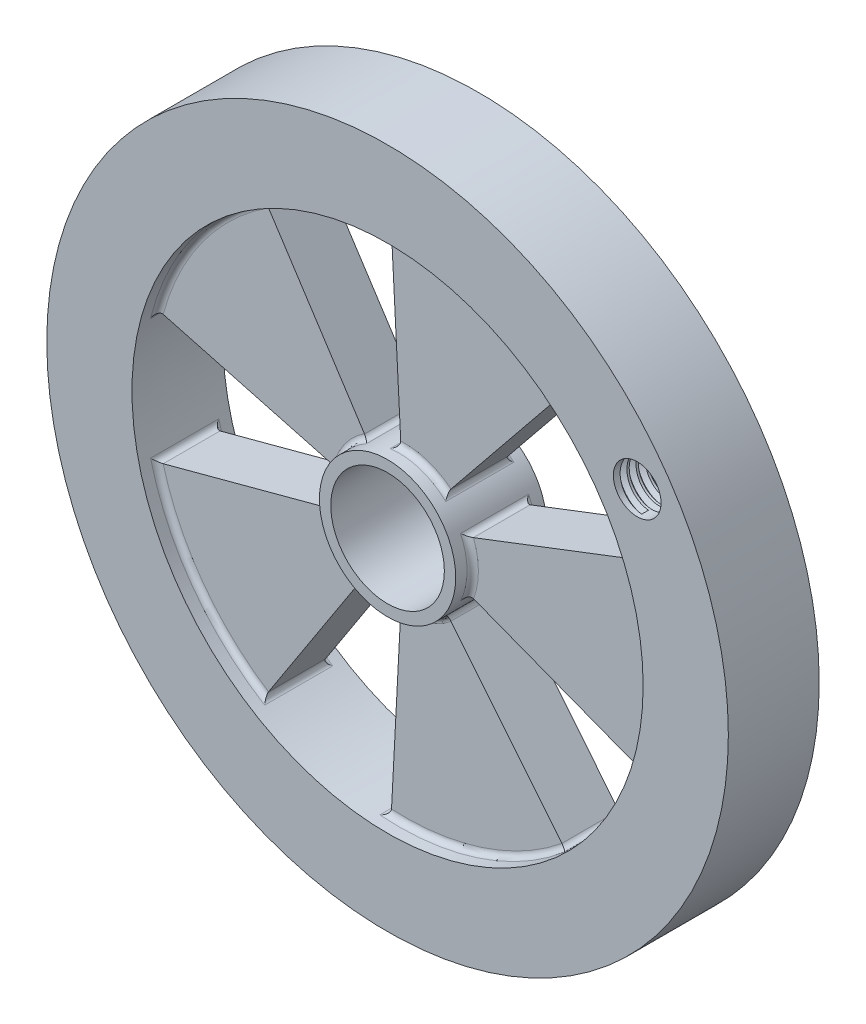
SolidWorks part; units mm, degrees
ref_plane "Front Plane" through (0, 0, 0) normal (0, 0, 1) x (1, 0, 0)
ref_plane "Top Plane" through (0, 0, 0) normal (0, 1, 0) x (1, 0, 0)
ref_plane "Right Plane" through (0, 0, 0) normal (1, 0, 0) x (0, 0, -1)
sketch "Sketch6" plane through (0, 0, 0) normal (0, 0, 1) x (1, 0, 0)
  circle A0 centre (0, 0) radius 30
  circle A1 centre (0, 0) radius 22.5
  circle A2 centre (0, 0) radius 6
  circle A3 centre (0, 0) radius 5
  dimension "D1" = 60
  dimension "D2" = 45
  dimension "D3" = 12
  dimension "D4" = 10
extrude "Boss-Extrude7" add sketch "Sketch6" along normal mid plane 8 contours A0 A1 | A2 A3 region at (-29.1515, 0, 0) region at (-5.8303, 0, 0)
sketch "Sketch8" plane through (0, 0, 0) normal (0, 0, 1) x (1, 0, 0)
  line L0 (6, 0) -> (49.2708, 0) construction
  line L1 (5.6015, 2.1502) -> (21.0056, 8.0633)
  line L2 (5.6015, -2.1502) -> (21.0056, -8.0633)
  circle A1 centre (0, 0) radius 22.5
  circle A2 centre (0, 0) radius 6
  dimension "D3" = 12
  dimension "D1" = 21
  dimension "D2" = 21
extrude "Boss-Extrude14" add sketch "Sketch8" along normal mid plane 5 contours A2 L0 A1 L1 | L0 A2 L2 A1 region at (15.4898, 2.8709, 0) region at (15.4898, -2.8709, 0)
fillet "Fillet5" radius 0.5 4 edges at (5.6015, -2.1502, 0) (5.6015, 2.1502, 0) (21.0056, -8.0633, 0) (21.0056, 8.0633, 0)
fillet "Fillet6" radius 0.5 2 edges at (22.5, 0, -2.5) (22.5, 0, 2.5)
fillet "Fillet7" radius 0.5 2 edges at (6, 0, -2.5) (6, 0, 2.5)
pattern_circular "CirPattern1" count 5 over 360 about axis through (0, 0, -4) along (0, 0, 1) of "Boss-Extrude14", "Fillet7", "Fillet6", "Fillet5"
hole_wizard "M5 Tapped Hole1" positions "Sketch10" profile "Sketch11" tap size "M5" standard "ISO"
sketch "Sketch10" plane through (0, 0, -4) normal (0, 0, -1) x (-1, 0, 0)
  point P0 (-21.9752, 14.7273)
sketch "Sketch11" plane through (21.9752, 14.7273, -4) normal (1, 0, 0) x (0, 1, 0)
  line L0 (0, 0) -> (0, 15.2618)
  line L1 (0, 15.2618) -> (2.1, 14)
  line L2 (2.1, 14) -> (2.1, 0)
  line L5 (2.1, 0) -> (0, 0)
  line L10 (0, 15.2618) -> (-2.1, 14) construction
  line L11 (0, -6.35) -> (0, 107.95) construction
  dimension "Tap Drill Dia." = 4.2
  dimension "Tap Drill Depth" = 14
  dimension "Drill Angle" = 118
cosmetic thread "Hole Thread1" parameters "D1"=10, "D2"=5
thread "Thread1" pitch 0.8 method cut profile "Thread Profile1" start angle 0, offset 0, length 7, pitch 0.8, diameter 4.2
ref_plane "Plane1" through (24.0752, 14.7273, -4) normal (0, -1, 0) x (1, 0, 0)
sketch "Thread Profile1" plane through (24.0752, 14.7273, -4) normal (0, -1, 0) x (1, 0, 0)
  line L0 (0, 0) -> (0, 0.8) construction
  line L1 (0, 0) -> (0.433, 0.25)
  line L2 (0.433, 0.25) -> (0.433, 0.35)
  line L3 (0.433, 0.35) -> (0, 0.6)
  line L4 (0.433, 0.3) -> (0, 0.3) construction
  line L11 (0, 0) -> (0, 0.6)
  point P2 (0, 0)
  dimension "Pitch" = 0.8
  dimension "Profile_Angle" = 60
  dimension "Profile_Land" = 0.1
  dimension "Profile_Height" = 0.433
